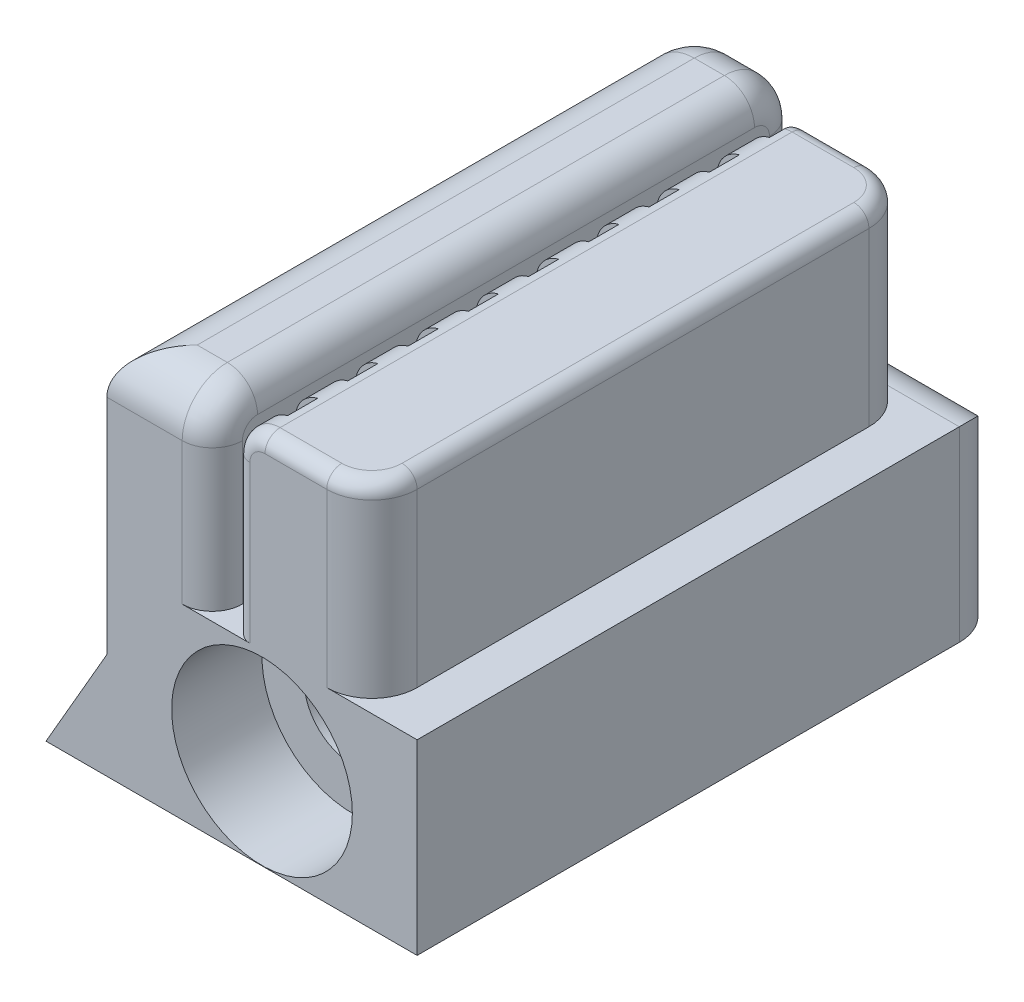
SolidWorks part; units mm, degrees
ref_plane "Front Plane" through (0, 0, 0) normal (0, 0, 1) x (1, 0, 0)
ref_plane "Top Plane" through (0, 0, 0) normal (0, 1, 0) x (1, 0, 0)
ref_plane "Right Plane" through (0, 0, 0) normal (1, 0, 0) x (0, 0, -1)
sketch "Sketch1" plane through (0, 0, 0) normal (0, 0, 1) x (1, 0, 0)
  line L0 (0, 0) -> (10.3, 0)
  line L1 (10.3, 0) -> (10.3, 12.4)
  line L2 (10.3, 12.4) -> (0, 12.4)
  line L3 (0, 12.4) -> (0, 0)
  dimension "D1" = 10.3
  dimension "D2" = 12.4
extrude "Boss-Extrude1" add sketch "Sketch1" along normal blind 19.5
sketch "Sketch2" plane through (0, 0, 19.5) normal (0, 0, 1) x (1, 0, 0)
  line L0 (0, 0) -> (-2.0207, 0)
  line L1 (-2.0207, 0) -> (0, 3.5)
  line L2 (0, 12.4) -> (0, 0) construction
  line L3 (0, 3.5) -> (0, 0)
  dimension "D1" = 60
  dimension "D2" = 3.5
extrude "Boss-Extrude2" add sketch "Sketch2" against normal blind 6
sketch "Sketch3" plane through (0, 12.4, 0) normal (0, 1, 0) x (1, 0, 0)
  line L0 (3.5, -19.5) -> (3.5, 0)
  line L1 (10.3, -19.5) -> (0, -19.5) construction
  line L2 (10.3, 0) -> (0, 0) construction
  line L3 (3.5, 0) -> (10.3, 0)
  line L4 (10.3, 0) -> (10.3, -19.5)
  line L5 (10.3, -19.5) -> (10.3, 0) construction
  line L6 (10.3, -19.5) -> (8.8, -19.5)
  line L7 (8.8, -19.5) -> (8.8, -1.5)
  line L8 (8.8, -1.5) -> (5, -1.5)
  line L9 (5, -1.5) -> (5, -2.5)
  line L10 (5, -2.5) -> (4.25, -2.5)
  line L11 (4.25, -2.5) -> (4.25, -3.5)
  line L12 (4.25, -3.5) -> (5, -3.5)
  line L13 (5, -3.5) -> (5, -4.5)
  line L14 (5, -4.5) -> (4.25, -4.5)
  line L15 (4.25, -4.5) -> (4.25, -5.5)
  line L16 (4.25, -5.5) -> (5, -5.5)
  line L17 (5, -5.5) -> (5, -6.5)
  line L18 (5, -6.5) -> (4.25, -6.5)
  line L19 (4.25, -6.5) -> (4.25, -7.5)
  line L20 (4.25, -7.5) -> (5, -7.5)
  line L21 (5, -7.5) -> (5, -8.5)
  line L22 (5, -8.5) -> (4.25, -8.5)
  line L23 (4.25, -8.5) -> (4.25, -9.5)
  line L24 (4.25, -9.5) -> (5, -9.5)
  line L25 (5, -9.5) -> (5, -10.5)
  line L26 (5, -10.5) -> (4.25, -10.5)
  line L27 (4.25, -10.5) -> (4.25, -11.5)
  line L28 (4.25, -11.5) -> (5, -11.5)
  line L29 (5, -11.5) -> (5, -12.5)
  line L30 (5, -12.5) -> (4.25, -12.5)
  line L31 (4.25, -12.5) -> (4.25, -13.5)
  line L32 (4.25, -13.5) -> (5, -13.5)
  line L33 (5, -13.5) -> (5, -14.5)
  line L34 (5, -14.5) -> (4.25, -14.5)
  line L35 (4.25, -14.5) -> (4.25, -15.5)
  line L36 (3.5, -19.5) -> (4.25, -19.5)
  line L37 (4.25, -15.5) -> (5, -15.5)
  line L38 (5, -15.5) -> (5, -16.5)
  line L39 (5, -16.5) -> (4.25, -16.5)
  line L40 (4.25, -16.5) -> (4.25, -17.5)
  line L41 (4.25, -17.5) -> (5, -17.5)
  line L42 (5, -17.5) -> (5, -18.5)
  line L43 (5, -18.5) -> (4.25, -18.5)
  line L44 (4.25, -18.5) -> (4.25, -19.5)
  line L45 (0, -19.5) -> (0, 0) construction
  dimension "D1" = 1.5
  dimension "D2" = 3.5
  dimension "D3" = 1
  dimension "D4" = 0.75
  dimension "D5" = 3.8
extrude "Cut-Extrude1" cut sketch "Sketch3" against normal blind 6.2
fillet "Fillet1" radius 1 4 edges at (4.25, 12.4, 19) (3.5, 9.3, 0) (3.5, 9.3, 19.5) (3.5, 12.4, 9.75)
fillet "Fillet3" radius 1.5 11 edges at (8.8, 9.3, 19.5) (1.25, 12.4, 19.5) (-1.0104, 1.75, 13.5) (6.4, 6.2, 0) (0, 12.4, 9.75) (1.25, 12.4, 0) (0, 6.2, 0) (10.3, 3.1, 0) (8.8, 9.3, 1.5) (3.2071, 12.1071, 0.2929) (3.2071, 12.1071, 19.2071)
fillet "Fillet4" radius 0.5 8 edges at (6.275, 12.4, 1.5) (8.3607, 12.4, 1.9393) (4.25, 8.8, 19.5) (4.5429, 12.1071, 19.5) (6.275, 12.4, 19.5) (8.3607, 12.4, 19.0607) (5, 9.2841, 1.5) (8.8, 12.4, 10.5)
sketch "Sketch5" plane through (0, 0, 19.5) normal (0, 0, 1) x (1, 0, 0)
  line L0 (0, 3.5) -> (0, 0) construction
  line L1 (0, 0) -> (10.3, 0) construction
  line L2 (5.15, 0) -> (5.15, 3.01) construction
  circle A0 centre (5.15, 3.01) radius 1.6
  dimension "D1" = 3.2
  dimension "D2" = 3.01
extrude "Cut-Extrude2" cut sketch "Sketch5" against normal up to next
sketch "Sketch6" plane through (0, 0, 19.5) normal (0, 0, 1) x (1, 0, 0)
  circle A0 centre (5.15, 3.01) radius 3
  dimension "D1" = 6
extrude "Cut-Extrude3" cut sketch "Sketch6" against normal blind 3
